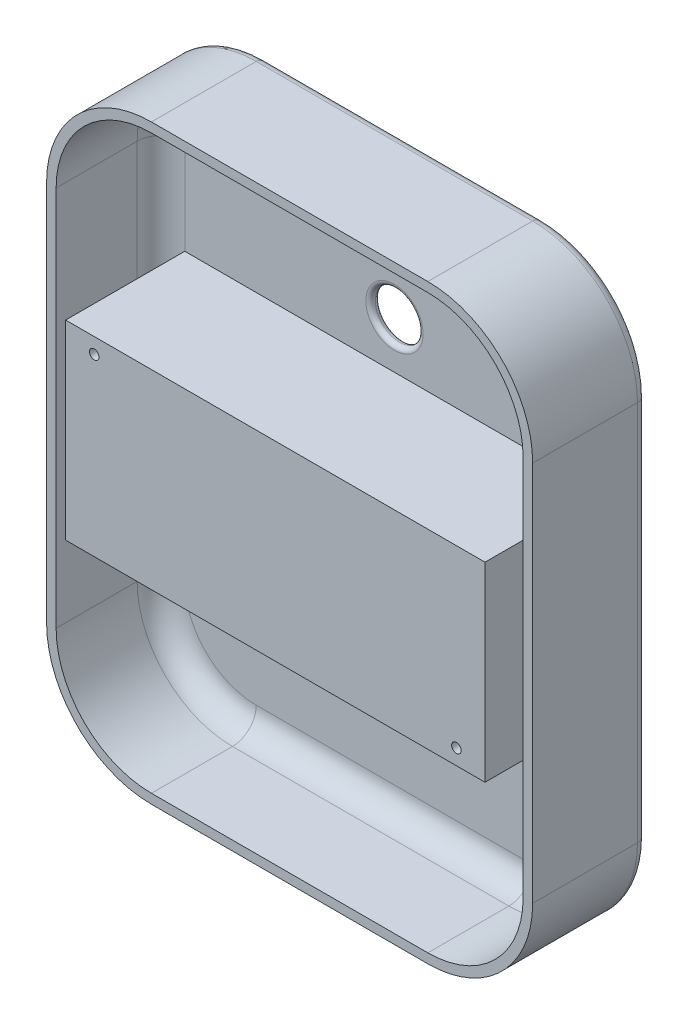
SolidWorks part; units mm, degrees
ref_plane "Front Plane" through (0, 0, 0) normal (0, 0, 1) x (1, 0, 0)
ref_plane "Top Plane" through (0, 0, 0) normal (0, 1, 0) x (1, 0, 0)
ref_plane "Right Plane" through (0, 0, 0) normal (1, 0, 0) x (0, 0, -1)
sketch "Sketch1" plane through (0, 0, 0) normal (0, 0, 1) x (1, 0, 0)
  line L0 (0, 60) -> (0, -60) construction
  line L5 (-29, 60) -> (29, 60)
  line L6 (-49, 40) -> (-49, -40)
  line L7 (-29, -60) -> (29, -60)
  line L8 (49, 40) -> (49, -40)
  line L9 (-49, 0) -> (49, 0) construction
  line L10 (-29, 62) -> (29, 62)
  line L11 (51, 40) -> (51, -40)
  line L12 (-29, -62) -> (29, -62)
  line L13 (-51, 40) -> (-51, -40)
  arc A2 (49, 40) -> (29, 60) centre (29, 40) ccw
  arc A3 (49, -40) -> (29, -60) centre (29, -40) cw
  arc A4 (-29, -60) -> (-49, -40) centre (-29, -40) cw
  arc A5 (-49, 40) -> (-29, 60) centre (-29, 40) cw
  arc A6 (51, 40) -> (29, 62) centre (29, 40) ccw
  arc A7 (51, -40) -> (29, -62) centre (29, -40) cw
  arc A8 (-29, -62) -> (-51, -40) centre (-29, -40) cw
  arc A9 (-51, 40) -> (-29, 62) centre (-29, 40) cw
  point P17 (49, 60)
  point P23 (-49, -60)
  point P26 (-49, 60)
  dimension "D5" = 20
  dimension "D3" = 98
  dimension "D4" = 120
  dimension "D6" = 2
extrude "Boss-Extrude1" add sketch "Sketch1" along normal blind 22
sketch "Sketch3" plane through (0, 0, 0) normal (0, 0, 1) x (1, 0, 0)
  line L0 (-44, -20) -> (-44, 20)
  line L1 (-44, -20) -> (44, -20)
  line L2 (44, -20) -> (44, 20)
  line L3 (-44, 20) -> (44, 20)
  line L4 (-44, 0) -> (44, 0) construction
  line L5 (0, 20) -> (0, -20) construction
  line L6 (-38, 16.75) -> (-38, 0) construction
  line L7 (38, -16.75) -> (38, 0) construction
  line L8 (-38, 16.75) -> (0, 16.75) construction
  line L9 (38, -16.75) -> (0, -16.75) construction
  circle A3 centre (-38, 16.75) radius 1
  circle A4 centre (38, -16.75) radius 1
  dimension "D5" = 2
  dimension "D1" = 88
  dimension "D2" = 40
  dimension "D3" = 76
  dimension "D4" = 33.5
extrude "Boss-Extrude2" add sketch "Sketch3" along normal blind 25
sketch "Sketch6" plane through (0, 0, 0) normal (0, 0, 1) x (1, 0, 0)
  line L0 (-29, 62) -> (29, 62)
  line L1 (51, 40) -> (51, -40)
  line L2 (-29, -62) -> (29, -62)
  line L3 (-51, 40) -> (-51, -40)
  line L6 (0, 0) -> (7.7555, 0) construction
  arc A0 (51, 40) -> (29, 62) centre (29, 40) ccw
  arc A1 (51, -40) -> (29, -62) centre (29, -40) cw
  arc A2 (-29, -62) -> (-51, -40) centre (-29, -40) cw
  arc A3 (-51, 40) -> (-29, 62) centre (-29, 40) cw
  circle A4 centre (0, 41) radius 1.75
  circle A5 centre (0, -41) radius 1.75
  circle A6 centre (0, 30) radius 5
  circle A7 centre (0, -30) radius 5
  point P22 (0, 0)
  point P23 (0, 0)
  dimension "D2" = 3.5
  dimension "D3" = 10
  dimension "D1" = 82
  dimension "D4" = 30
extrude "Boss-Extrude3" add sketch "Sketch6" against normal blind 2 separate body
sketch "Sketch4" plane through (0, 0, 0) normal (0, 0, 1) x (1, 0, 0)
  line L1 (-37.5, 55) -> (37.5, 55)
  line L2 (-37.5, 55) -> (-37.5, -55)
  line L3 (-37.5, -55) -> (37.5, -55)
  line L4 (37.5, 55) -> (37.5, -55)
  line L5 (-28.5, 50) -> (28.5, 50)
  line L6 (-28.5, 50) -> (-28.5, -50)
  line L7 (-28.5, -50) -> (28.5, -50)
  line L8 (28.5, 50) -> (28.5, -50)
  point P4 (-37.5, 0)
  point P6 (0, 55)
  point P11 (0, 50)
  point P12 (-28.5, 0)
  dimension "D1" = 75
  dimension "D2" = 110
  dimension "D3" = 57
  dimension "D4" = 100
combine bodies "Combine1" operation type add bodies to combine 101 103
fillet "Fillet10" radius 5 8 edges at (49, 0, 0) (43.1421, -54.1421, 0) (0, -60, 0) (-43.1421, -54.1421, 0) (-49, 0, 0) (-43.1421, 54.1421, 0) (0, 60, 0) (43.1421, 54.1421, 0)
fillet "Fillet12" radius 2 8 edges at (-44.5563, -55.5563, -2) (0, -62, -2) (44.5563, -55.5563, -2) (51, 0, -2) (44.5563, 55.5563, -2) (0, 62, -2) (-51, 0, -2) (-44.5563, 55.5563, -2)
fillet "Fillet13" radius 1 2 edges at (5, 30, -2) (5, 30, 0)
fillet "Fillet14" radius 1 6 edges at (5, -30, 0) (1.75, 41, 0) (1.75, 41, -2) (1.75, -41, -2) (1.75, -41, 0) (5, -30, -2)
